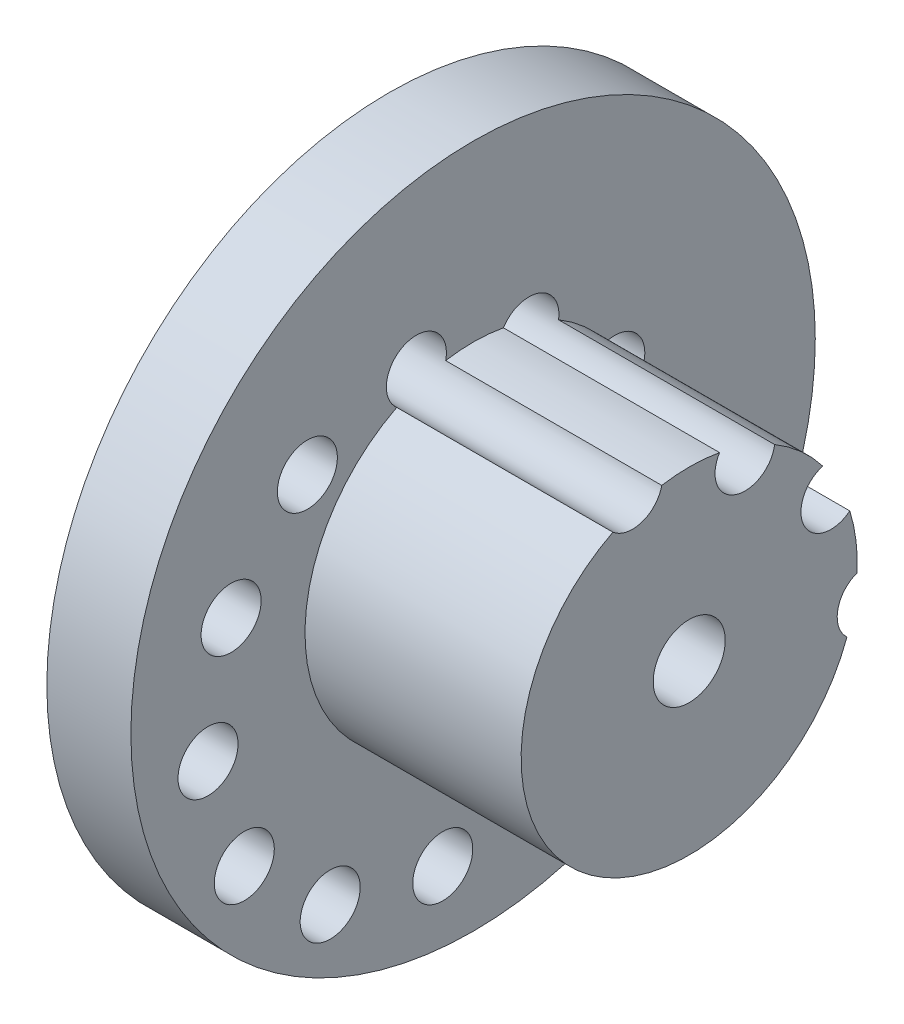
SolidWorks part; units mm, degrees
ref_plane "Front Plane" through (0, 0, 0) normal (0, 0, 1) x (1, 0, 0)
ref_plane "Top Plane" through (0, 0, 0) normal (0, 1, 0) x (1, 0, 0)
ref_plane "Right Plane" through (0, 0, 0) normal (1, 0, 0) x (0, 0, -1)
sketch "Sketch1" plane through (0, 0, 0) normal (1, 0, 0) x (0, 0, -1)
  circle A0 centre (0, 0) radius 28.5
  circle A1 centre (0, 0) radius 14
  circle A2 centre (0, 0) radius 3
  dimension "D1" = 6
  dimension "D2" = 57
  dimension "D3" = 28
extrude "Boss-Extrude1" add sketch "Sketch1" along normal blind 7 contours A0 A1 region at (0, 0, 27.6939)
extrude "Boss-Extrude2" add sketch "Sketch1<4>" along normal blind 25 contours A1 A2 region at (0, 0, 13.604)
sketch "Sketch1<4>" plane through (0, 0, 0) normal (1, 0, 0) x (0, 0, -1) same geometry as "Sketch1"
sketch "Sketch3" plane through (0, 0, 0) normal (-1, 0, 0) x (0, 0, 1)
  circle A0 centre (19.055, -14.26) radius 2.5
  circle A1 centre (11.9, -20.6114) radius 2.5
  circle A2 centre (2.5278, -22.5344) radius 2.5
  circle A3 centre (-6.5502, -19.5137) radius 2.5
  circle A4 centre (-12.9016, -12.3587) radius 2.5
  circle A5 centre (-14.8247, -2.9865) radius 2.5
  circle A6 centre (-11.804, 6.0915) radius 2.5
  circle A7 centre (-4.6489, 12.443) radius 2.5
  circle A8 centre (4.7232, 14.366) radius 2.5
  circle A9 centre (13.8013, 11.3453) radius 2.5
  circle A10 centre (20.1527, 4.1902) radius 2.5
  circle A11 centre (22.0757, -5.1819) radius 2.5
  point P27 (3.6255, -4.0842)
  dimension "D1" = 12
extrude "Cut-Extrude1" cut sketch "Sketch3" against normal through all both and the other way through all
